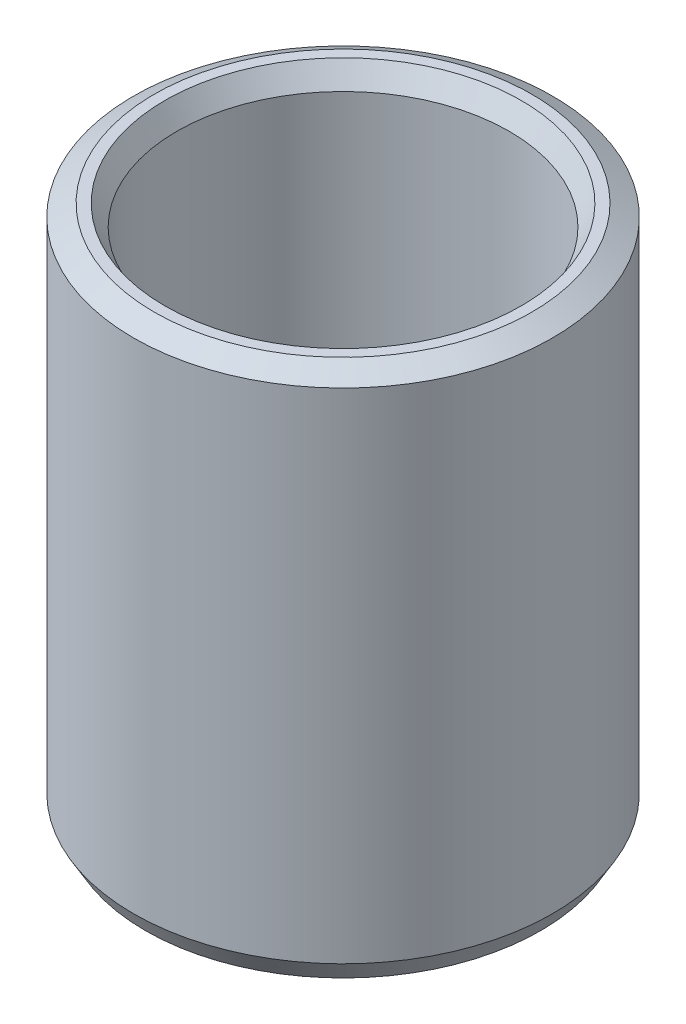
SolidWorks part; units mm, degrees
ref_plane "Front Plane" through (0, 0, 0) normal (0, 0, 1) x (1, 0, 0)
ref_plane "Top Plane" through (0, 0, 0) normal (0, 1, 0) x (1, 0, 0)
ref_plane "Right Plane" through (0, 0, 0) normal (1, 0, 0) x (0, 0, -1)
sketch "Sketch1" plane through (0, 0, 0) normal (0, 1, 0) x (1, 0, 0)
  circle A0 centre (0, 0) radius 60
  dimension "SLEEVE_OD" = 120
extrude "Boss-Extrude1" add sketch "Sketch1" along normal blind 152.1562
sketch "Sketch2" plane through (0, 0, 0) normal (0, 1, 0) x (1, 0, 0)
  circle A0 centre (0, 0) radius 47.5716
  dimension "BORE_D" = 95.1432
extrude "Cut-Extrude1" cut sketch "Sketch2" along normal through all
chamfer "Chamfer1" distance 3.4272 angle 60 4 edges at (0, 152.1562, 47.5716) (0, 0, 47.5716) (0, 0, 60) (0, 152.1562, 60) first distance on face at (0, 152.1562, 47.5716) first distance on face at (0, 0, 47.5716) first distance on face at (0, 152.1562, 60)
